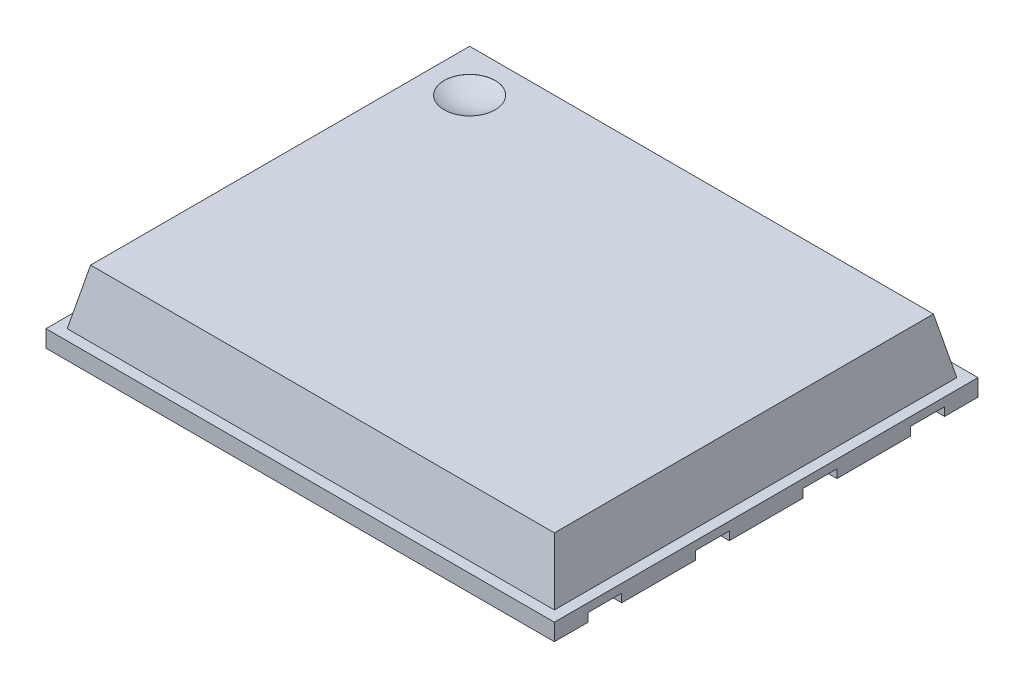
SolidWorks part; units mm, degrees
ref_plane "Front" through (0, 0, 0) normal (0, 0, 1) x (1, 0, 0)
ref_plane "Top" through (0, 0, 0) normal (0, 1, 0) x (1, 0, 0)
ref_plane "Right" through (0, 0, 0) normal (1, 0, 0) x (0, 0, -1)
sketch "Sketch1" plane through (0, 0, 0) normal (0, 1, 0) x (1, 0, 0)
  line L1 (3, -2.5) -> (-3, -2.5)
  line L2 (3, -2.5) -> (3, 2.5)
  line L3 (3, 2.5) -> (-3, 2.5)
  line L4 (-3, -2.5) -> (-3, 2.5)
  line L5 (3, -2.5) -> (-3, 2.5) construction
  line L6 (3, 2.5) -> (-3, -2.5) construction
  point P0 (0, 0)
  dimension "D1" = 6
  dimension "D2" = 5
extrude "Extrude1" add sketch "Sketch1" along normal blind 0.2
sketch "Sketch2" plane through (0, 0.2, 0) normal (0, 1, 0) x (-1, 0, 0)
  line L1 (-2.875, 2.375) -> (2.875, 2.375)
  line L2 (-2.875, 2.375) -> (-2.875, -2.375)
  line L3 (-2.875, -2.375) -> (2.875, -2.375)
  line L4 (2.875, 2.375) -> (2.875, -2.375)
  line L5 (-2.875, 2.375) -> (2.875, -2.375) construction
  line L6 (-2.875, -2.375) -> (2.875, 2.375) construction
  point P0 (0, 0)
  dimension "D1" = 5.75
  dimension "D2" = 4.75
extrude "Extrude2" add sketch "Sketch2" along normal blind 0.65 draft 12
sketch "Sketch3" plane through (0, 0.85, 0) normal (0, 1, 0) x (-1, 0, 0)
  line L0 (2.7368, -2.2368) -> (2.7368, 2.2368) construction
  line L1 (-2.7368, -2.2368) -> (2.7368, -2.2368) construction
  circle A0 centre (2.2368, -1.7368) radius 0.3009
  dimension "D1" = 0.5
  dimension "D2" = 0.5
extrude "Extrude3" cut sketch "Sketch3" against normal blind 0.001
dome "Dome1" faces to dome 1 distance 0.075 reverse direction yes elliptical dome no face at (-2.2368, 0.849, -1.436) parameters "D1"=0.075
sketch "Sketch4" plane through (0, 0, 0) normal (0, -1, 0) x (1, 0, 0)
  line L0 (-1.7, -1.6815) -> (-1.7, -2)
  line L1 (-1.7, 2) -> (1.7, 2)
  line L2 (-1.7, 2) -> (-1.7, -1.386)
  line L3 (-1.7, -2) -> (1.7, -2)
  line L4 (1.7, 2) -> (1.7, -2)
  line L5 (-1.7, 2) -> (1.7, -2) construction
  line L6 (-1.7, -2) -> (1.7, 2) construction
  arc A0 (-1.7, -1.6815) -> (-1.7, -1.386) centre (-1.7, -1.5338) ccw
  point P0 (0, 0)
  dimension "D1" = 4
  dimension "D2" = 3.4
extrude "Extrude4" cut sketch "Sketch4" against normal blind 0.1
fillet "Fillet1" radius 0.1 6 edges at (-1.7, 0.05, 2) (1.7, 0.05, 2) (-1.7, 0.05, -1.386) (-1.7, 0.05, -1.6815) (-1.7, 0.05, -2) (1.7, 0.05, -2)
sketch "Sketch5" plane through (0, 0, 0) normal (0, -1, 0) x (1, 0, 0)
  line L0 (3, 2.5) -> (3, -2.5) construction
  line L1 (3, 2.105) -> (2.6, 2.105)
  line L2 (3, 2.105) -> (3, 1.705)
  line L3 (3, 1.705) -> (2.6, 1.705)
  line L4 (3, 0.435) -> (2.6, 0.435)
  line L5 (3, 0.835) -> (2.6, 0.835)
  line L6 (3, 0.835) -> (3, 0.435)
  line L7 (3, -0.835) -> (2.6, -0.835)
  line L8 (3, -0.435) -> (2.6, -0.435)
  line L9 (3, -0.435) -> (3, -0.835)
  line L10 (3, -2.105) -> (2.6, -2.105)
  line L11 (3, -1.705) -> (2.6, -1.705)
  line L12 (3, -1.705) -> (3, -2.105)
  line L13 (3, -2.5) -> (3, -2.105) construction
  line L14 (3, 2.105) -> (3, 2.5) construction
  arc A0 (2.6, 1.705) -> (2.6, 2.105) centre (2.6, 1.905) cw
  arc A1 (2.6, 0.435) -> (2.6, 0.835) centre (2.6, 0.635) cw
  arc A2 (2.6, -0.835) -> (2.6, -0.435) centre (2.6, -0.635) cw
  arc A3 (2.6, -2.105) -> (2.6, -1.705) centre (2.6, -1.905) cw
  dimension "D1" = 0.6
  dimension "D2" = 0.4
  dimension "D3" = 1.27
extrude "Extrude5" cut sketch "Sketch5" against normal blind 0.1
mirror "Mirror1" about plane through (0, 0, 0) normal (1, 0, 0) of "Extrude5"
